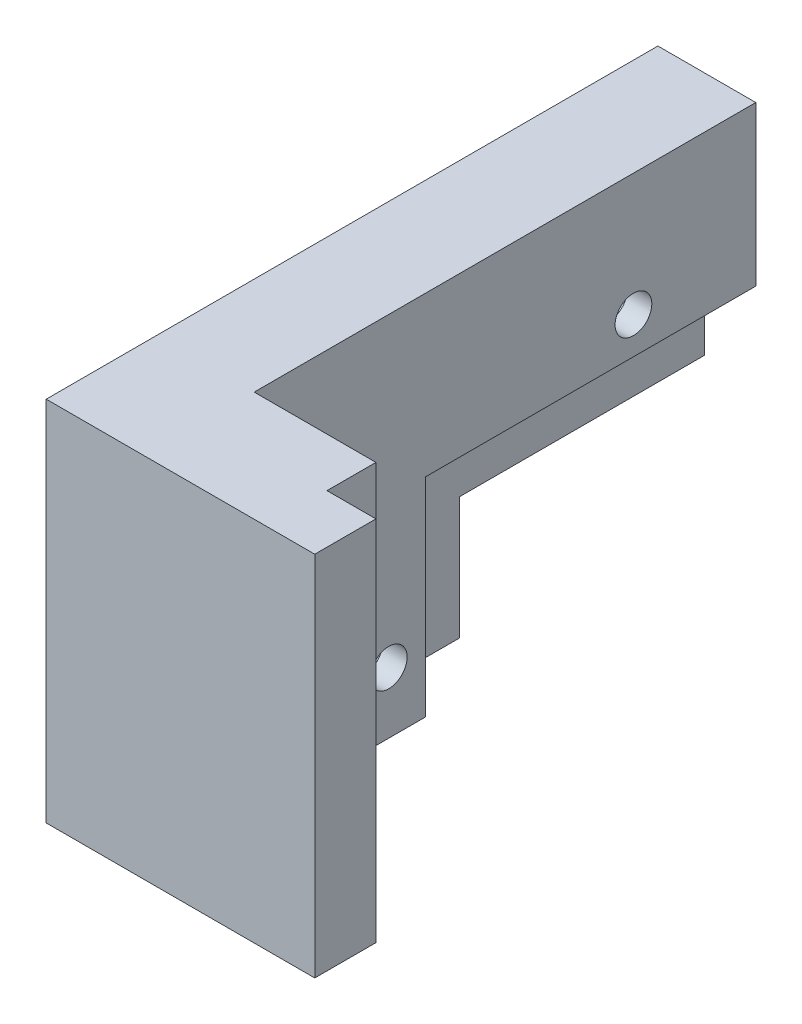
SolidWorks part; units mm, degrees
ref_plane "前视基准面" through (0, 0, 0) normal (0, 0, 1) x (1, 0, 0)
ref_plane "上视基准面" through (0, 0, 0) normal (0, 1, 0) x (1, 0, 0)
ref_plane "右视基准面" through (0, 0, 0) normal (1, 0, 0) x (0, 0, -1)
other "Configuration Table"
sketch "草图1" plane through (0, 0, 0) normal (0, 0, 1) x (1, 0, 0)
  line L1 (0, 0) -> (-40, 0)
  line L2 (0, 0) -> (0, 30)
  line L3 (0, 30) -> (-40, 30)
  line L4 (-40, 0) -> (-40, 30)
  dimension "D1" = 40
  dimension "D2" = 30
extrude "凸台-拉伸1" add sketch "草图1" along normal blind 5
sketch "草图2" plane through (-40, 0, 0) normal (-1, 0, 0) x (0, 0, 1)
  line L4 (0, 30) -> (0, 0)
  line L5 (0, 0) -> (5, 0)
  line L6 (5, 0) -> (5, 30)
  line L7 (5, 30) -> (0, 30)
  line L8 (0, 30) -> (0, 0)
  line L9 (0, 0) -> (5, 0)
  line L10 (5, 0) -> (5, 30)
  line L11 (5, 30) -> (0, 30)
  dimension "D1" = 0
extrude "凸台-拉伸2" add sketch "草图2" along normal blind 20
sketch "草图3" plane through (0, 0, 0) normal (0, 0, -1) x (-1, 0, 0)
  line L0 (60, 0) -> (0, 0) construction
  line L1 (60, 30) -> (40, 30)
  line L2 (60, 30) -> (60, 0)
  line L3 (60, 0) -> (40, 0)
  line L4 (40, 30) -> (40, 0)
  dimension "D1" = 20
extrude "凸台-拉伸3" add sketch "草图3" along normal blind 5
sketch "草图4" plane through (0, 0, 5) normal (0, 0, 1) x (1, 0, 0)
  line L0 (0, 30) -> (-60, 30) construction
  line L1 (-60, 30) -> (-45, 30)
  line L2 (-60, 30) -> (-60, 0)
  line L3 (-60, 0) -> (-45, 0)
  line L4 (-45, 30) -> (-45, 0)
  line L5 (-60, 0) -> (0, 0) construction
  line L6 (-60, 0) -> (-60, 30) construction
  dimension "D1" = 0
  dimension "D2" = 15
extrude "切除-拉伸1" cut sketch "草图4" against normal blind 5
sketch "草图5" plane through (0, 0, 0) normal (0, 0, 1) x (1, 0, 0)
  line L0 (-52.5, 30) -> (-52.5, 25) construction
  line L1 (-45, 30) -> (-60, 30) construction
  line L2 (-52.5, 25) -> (-52.5, 5) construction
  circle A0 centre (-52.5, 5) radius 1.5
  circle A1 centre (-52.5, 25) radius 1.5
  dimension "D3" = 3
  dimension "D4" = 3
  dimension "D1" = 5
  dimension "D2" = 20
extrude "切除-拉伸2" cut sketch "草图5" against normal blind 5
sketch "草图6" plane through (0, 0, 0) normal (0, 0, 1) x (1, 0, 0)
  circle A0 centre (-52.5, 25) radius 3
  circle A1 centre (-52.5, 5) radius 3
  dimension "D1" = 6
  dimension "D2" = 6
extrude "切除-拉伸3" cut sketch "草图6" against normal blind 2
sketch "草图7" plane through (0, 0, 0) normal (0, 0, 1) x (1, 0, 0)
  line L4 (-60, 30) -> (-60, 0)
  line L5 (-60, 0) -> (-45, 0)
  line L6 (-45, 0) -> (-45, 30)
  line L7 (-45, 30) -> (-60, 30)
  line L8 (-60, 30) -> (-60, 0)
  line L9 (-60, 0) -> (-45, 0)
  line L10 (-45, 0) -> (-45, 30)
  line L11 (-45, 30) -> (-60, 30)
  dimension "D1" = 0
extrude "切除-拉伸4" cut sketch "草图7" against normal blind 10
sketch "草图8" plane through (0, 0, -5) normal (0, 0, -1) x (-1, 0, 0)
  line L4 (40, 0) -> (45, 0)
  line L5 (45, 0) -> (45, 30)
  line L6 (45, 30) -> (40, 30)
  line L7 (40, 30) -> (40, 0)
  line L8 (40, 0) -> (45, 0)
  line L9 (45, 0) -> (45, 30)
  line L10 (45, 30) -> (40, 30)
  line L11 (40, 30) -> (40, 0)
  dimension "D1" = 0
extrude "凸台-拉伸4" add sketch "草图8" along normal blind 20
sketch "草图9" plane through (-40, 0, 0) normal (1, 0, 0) x (0, 0, -1)
  line L0 (25, 0) -> (0, 0) construction
  line L1 (25, 30) -> (18, 30)
  line L2 (25, 30) -> (25, 0)
  line L3 (25, 0) -> (18, 0)
  line L4 (18, 30) -> (18, 0)
  dimension "D1" = 7
sketch "草图10" plane through (-45, 0, 0) normal (-1, 0, 0) x (0, 0, 1)
  line L4 (5, 0) -> (5, 30)
  line L5 (5, 30) -> (-25, 30)
  line L6 (-25, 30) -> (-25, 0)
  line L7 (-25, 0) -> (5, 0)
  line L8 (5, 0) -> (5, 30)
  line L9 (5, 30) -> (-25, 30)
  line L10 (-25, 30) -> (-25, 0)
  line L11 (-25, 0) -> (5, 0)
  dimension "D1" = 0
extrude "凸台-拉伸5" add sketch "草图10" along normal blind 3
sketch "草图11" plane through (-48, 0, 0) normal (-1, 0, 0) x (0, 0, 1)
  line L0 (-25, 30) -> (-15, 30) construction
  line L1 (5, 30) -> (-25, 30) construction
  line L2 (-15, 30) -> (-15, 5) construction
  circle A0 centre (-15, 5) radius 1.5
  dimension "D4" = 3
  dimension "D1" = 25
  dimension "D3" = 10
extrude "切除-拉伸6" cut sketch "草图11" against normal blind 13
sketch "草图12" plane through (-48, 0, 0) normal (-1, 0, 0) x (0, 0, 1)
  circle A0 centre (-15, 5) radius 2.9
  dimension "D1" = 5.8
extrude "切除-拉伸7" cut sketch "草图12" against normal offset from surface (6 mm away) 2 up to face at (-40, 5, -13.5)
sketch "草图14" plane through (0, 0, -25) normal (0, 0, -1) x (-1, 0, 0)
  line L0 (40, 30) -> (40, 0) construction
  line L1 (48, 30) -> (40, 30)
  line L2 (48, 30) -> (48, 10)
  line L3 (48, 10) -> (40, 10)
  line L4 (40, 30) -> (40, 10)
  dimension "D1" = 20
extrude "凸台-拉伸6" add sketch "草图14" along normal blind 20
sketch "草图15" plane through (-40, 0, 0) normal (1, 0, 0) x (0, 0, -1)
  line L1 (45, 10) -> (25, 10)
  line L2 (45, 10) -> (45, 17)
  line L3 (45, 17) -> (18, 17)
  line L4 (18, 10) -> (18, 17)
  line L6 (18, 10) -> (18, 0)
  line L7 (18, 0) -> (25, 0)
  line L8 (25, 10) -> (25, 0)
  dimension "D1" = 7
  dimension "D2" = 7
extrude "切除-拉伸8" cut sketch "草图15" against normal blind 4.2
sketch "草图16" plane through (-48, 0, 0) normal (-1, 0, 0) x (0, 0, 1)
  line L0 (-45, 30) -> (-45, 20) construction
  line L1 (-45, 10) -> (-45, 30) construction
  line L2 (-45, 20) -> (-35, 20) construction
  circle A0 centre (-35, 20) radius 1.5
  dimension "D3" = 3
  dimension "D1" = 10
  dimension "D2" = 10
extrude "切除-拉伸9" cut sketch "草图16" against normal blind 14.2
sketch "草图17" plane through (-48, 0, 0) normal (-1, 0, 0) x (0, 0, 1)
  circle A0 centre (-35, 20) radius 2.9
  dimension "D1" = 5.8
extrude "切除-拉伸10" cut sketch "草图17" against normal offset from surface (6 mm away) 2 up to face at (-40, 20, -33.5)
sketch "草图18" plane through (-40, 0, 0) normal (1, 0, 0) x (0, 0, -1)
  line L0 (18, 0) -> (0, 0) construction
  line L1 (0, 30) -> (4, 30)
  line L2 (0, 30) -> (0, 0)
  line L3 (0, 0) -> (4, 0)
  line L4 (4, 30) -> (4, 0)
  dimension "D1" = 4
extrude "凸台-拉伸7" add sketch "草图18" along normal blind 9.95
sketch "草图19" plane through (0, 0, 0) normal (1, 0, 0) x (0, 0, -1)
  line L4 (0, 0) -> (0, 30)
  line L5 (0, 30) -> (-5, 30)
  line L6 (-5, 30) -> (-5, 0)
  line L7 (-5, 0) -> (0, 0)
  line L8 (0, 0) -> (0, 30)
  line L9 (0, 30) -> (-5, 30)
  line L10 (-5, 30) -> (-5, 0)
  line L11 (-5, 0) -> (0, 0)
  dimension "D1" = 0
extrude "切除-拉伸11" cut sketch "草图19" against normal offset from surface (26.05 mm away) 4 up to face at (-30.05, 15, -2)
